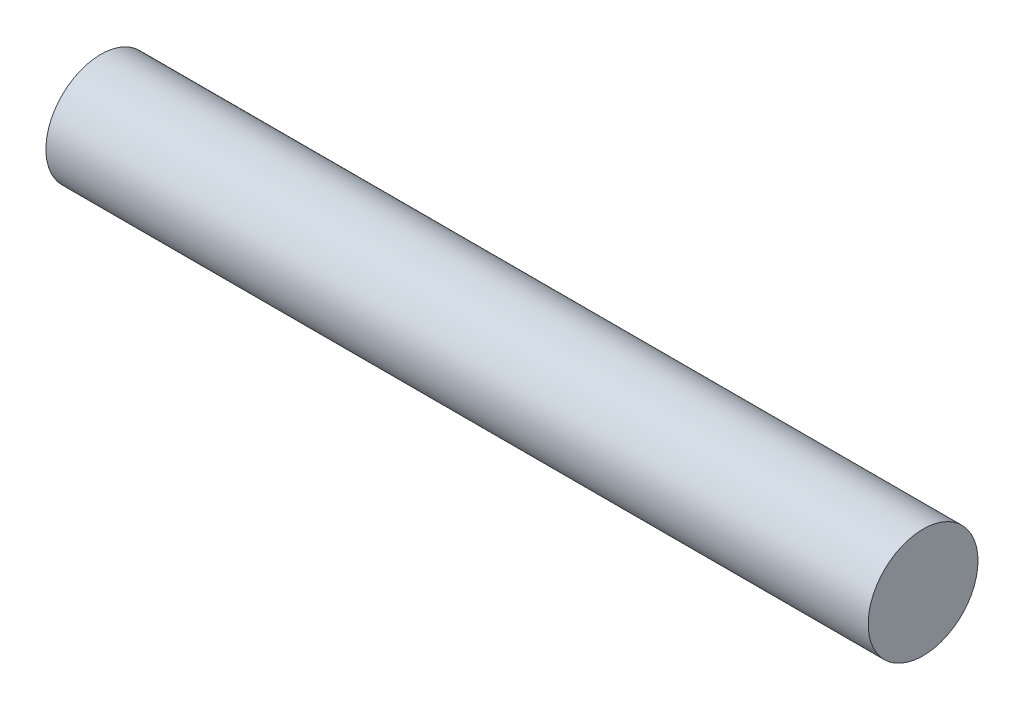
SolidWorks part; units mm, degrees
ref_plane "Front Plane" through (0, 0, 0) normal (0, 0, 1) x (1, 0, 0)
ref_plane "Top Plane" through (0, 0, 0) normal (0, 1, 0) x (1, 0, 0)
ref_plane "Right Plane" through (0, 0, 0) normal (1, 0, 0) x (0, 0, -1)
sketch "Sketch1" plane through (0, 0, 0) normal (0, 0, 1) x (1, 0, 0)
  line L0 (0, 0) -> (299.4969, 0)
sketch "Sketch2" plane through (0, 0, 0) normal (1, 0, 0) x (0, 0, -1)
  circle A0 centre (0, 0) radius 20
  dimension "D1" = 40
sweep "Sweep1" add path "Sketch1" circular profile diameter 40 parameters "D3"=40
